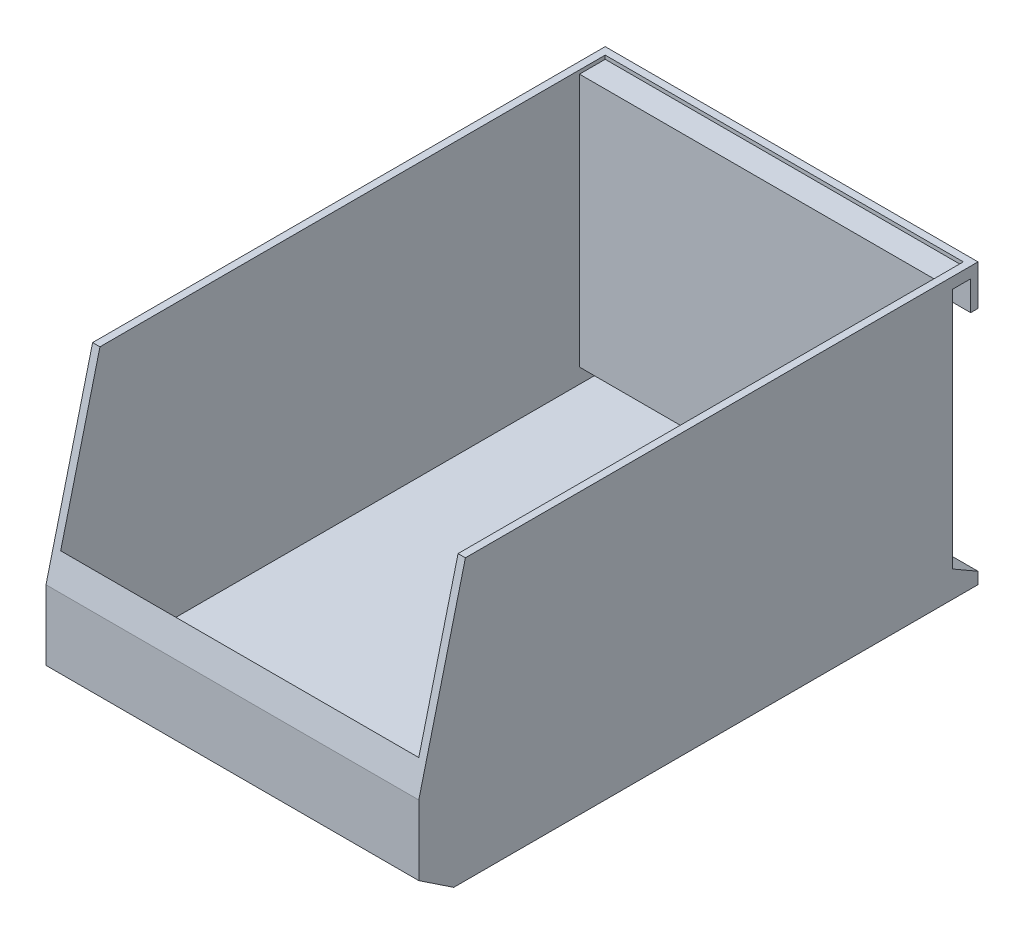
SolidWorks part; units mm, degrees
ref_plane "Front Plane" through (0, 0, 0) normal (0, 0, 1) x (1, 0, 0)
ref_plane "Top Plane" through (0, 0, 0) normal (0, 1, 0) x (1, 0, 0)
ref_plane "Right Plane" through (0, 0, 0) normal (1, 0, 0) x (0, 0, -1)
sketch "Sketch1" plane through (0, 0, 0) normal (0, 1, 0) x (1, 0, 0)
  line L1 (-50.8, -76.2) -> (50.8, -76.2)
  line L2 (-50.8, -76.2) -> (-50.8, 76.2)
  line L3 (-50.8, 76.2) -> (50.8, 76.2)
  line L4 (50.8, -76.2) -> (50.8, 76.2)
  line L5 (-50.8, -76.2) -> (50.8, 76.2) construction
  line L6 (-50.8, 76.2) -> (50.8, -76.2) construction
  point P0 (0, 0)
  dimension "D1" = 152.4
  dimension "D2" = 101.6
extrude "Boss-Extrude1" add sketch "Sketch1" along normal blind 76.2
sketch "Sketch2" plane through (50.8, 0, 0) normal (1, 0, 0) x (0, 0, -1)
  line L0 (-63.5, 76.2) -> (-76.2, 25.4)
  line L1 (-76.2, 76.2) -> (76.2, 76.2) construction
  line L2 (-76.2, 76.2) -> (-76.2, 0) construction
  line L3 (-76.2, 6.35) -> (-76.2, 0)
  line L4 (-76.2, 6.35) -> (-66.675, 0)
  line L5 (-76.2, 0) -> (76.2, 0) construction
  line L6 (-76.2, 0) -> (-66.675, 0)
  line L7 (-76.2, 25.4) -> (-76.2, 76.2)
  line L8 (-76.2, 76.2) -> (-63.5, 76.2)
  dimension "D1" = 12.7
  dimension "D2" = 9.525
  dimension "D3" = 19.05
  dimension "D4" = 6.35
extrude "Cut-Extrude1" cut sketch "Sketch2" against normal through all
sketch "Sketch3" plane through (50.8, 0, 0) normal (1, 0, 0) x (0, 0, -1)
  line L0 (76.2, 76.2) -> (76.2, 0) construction
  line L1 (76.2, 7.2165) -> (69.2, 7.2165) construction
  line L3 (76.2, 65.2) -> (69.2, 65.2) construction
  line L4 (69.2, 7.2165) -> (69.2, 65.2)
  line L5 (69.2, 7.2165) -> (76.2, 3.175)
  line L6 (69.2, 65.2) -> (69.2, 73.2)
  line L7 (69.2, 73.2) -> (74.2, 73.2)
  line L8 (74.2, 73.2) -> (74.2, 65.2)
  line L9 (74.2, 65.2) -> (76.2, 65.2)
  line L10 (76.2, 65.2) -> (76.2, 3.175)
  line L11 (-63.5, 76.2) -> (76.2, 76.2) construction
  dimension "D1" = 7
  dimension "D2" = 3.175
  dimension "D3" = 30
  dimension "D4" = 2
  dimension "D5" = 3
  dimension "D6" = 8
extrude "Cut-Extrude2" cut sketch "Sketch3" against normal through all
shell "Shell1" thickness 2 removed face at (0, 76.2, -6.35) removed face at (0, 50.8, 69.85)
